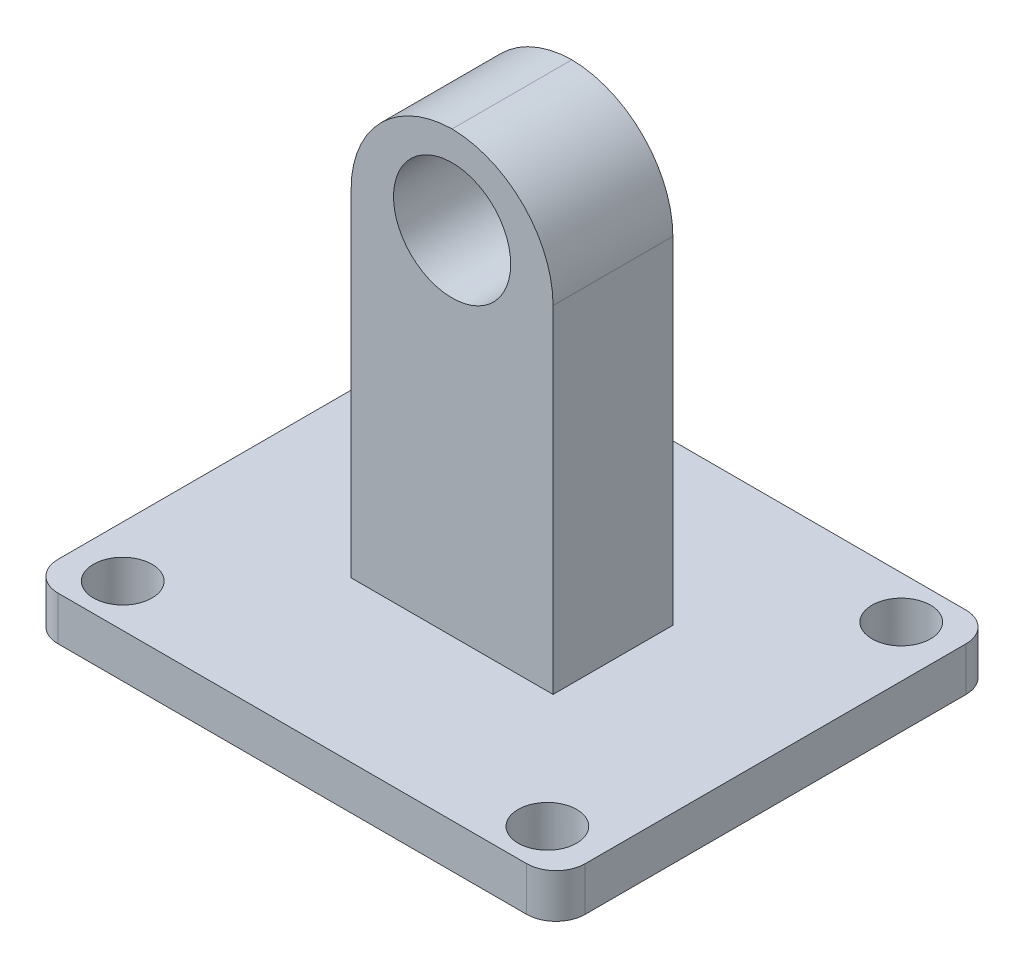
SolidWorks part; units mm, degrees
ref_plane "Front Plane" through (0, 0, 0) normal (0, 0, 1) x (1, 0, 0)
ref_plane "Top Plane" through (0, 0, 0) normal (0, 1, 0) x (1, 0, 0)
ref_plane "Right Plane" through (0, 0, 0) normal (1, 0, 0) x (0, 0, -1)
sketch "Sketch1" plane through (0, 0, 0) normal (0, 1, 0) x (1, 0, 0)
  line L1 (-18, -15) -> (18, -15)
  line L2 (-18, -15) -> (-18, 15)
  line L3 (-18, 15) -> (18, 15)
  line L4 (18, -15) -> (18, 15)
  line L5 (-18, -15) -> (18, 15) construction
  line L6 (-18, 15) -> (18, -15) construction
  circle A0 centre (-14.5, 12.0833) radius 2
  circle A1 centre (14.5, 12.0833) radius 2
  circle A2 centre (14.5, -12.0833) radius 2
  circle A3 centre (-14.5, -12.0833) radius 2
  point P0 (0, 0)
  dimension "D7" = 4
  dimension "D1" = 36
  dimension "D2" = 30
  dimension "D3" = 3.5
  dimension "D4" = 3.5
  dimension "D5" = 3.5
  dimension "D6" = 3.5
extrude "Boss-Extrude1" add sketch "Sketch1" along normal blind 3 contours L3 L4 L1 L2
sketch "Sketch2" plane through (0, 3, 0) normal (0, 1, 0) x (1, 0, 0)
  line L1 (-6.8947, -4.0905) -> (6.8947, -4.0905)
  line L2 (-6.8947, -4.0905) -> (-6.8947, 4.0905)
  line L3 (-6.8947, 4.0905) -> (6.8947, 4.0905)
  line L4 (6.8947, -4.0905) -> (6.8947, 4.0905)
  line L5 (-6.8947, -4.0905) -> (6.8947, 4.0905) construction
  line L6 (-6.8947, 4.0905) -> (6.8947, -4.0905) construction
  point P0 (0, 0)
extrude "Boss-Extrude2" add sketch "Sketch2" along normal blind 30
fillet "Fillet1" radius 2 4 edges at (-18, 1.5, 15) (-18, 1.5, -15) (18, 1.5, -15) (18, 1.5, 15)
fillet "Fillet2" radius 7 2 edges at (6.8947, 33, 0) (-6.8947, 33, 0)
sketch "Sketch3" plane through (0, 0, 4.0905) normal (0, 0, 1) x (1, 0, 0)
  circle A0 centre (0, 27) radius 4
  dimension "D1" = 8
  dimension "D2" = 27
extrude "Cut-Extrude1" cut sketch "Sketch3" against normal blind 13
extrude "Cut-Extrude2" cut sketch "Sketch1<4>" along normal blind 4 contours A1 | A2 | A3 | A0
sketch "Sketch1<4>" plane through (0, 0, 0) normal (0, 1, 0) x (1, 0, 0) same geometry as "Sketch1"
